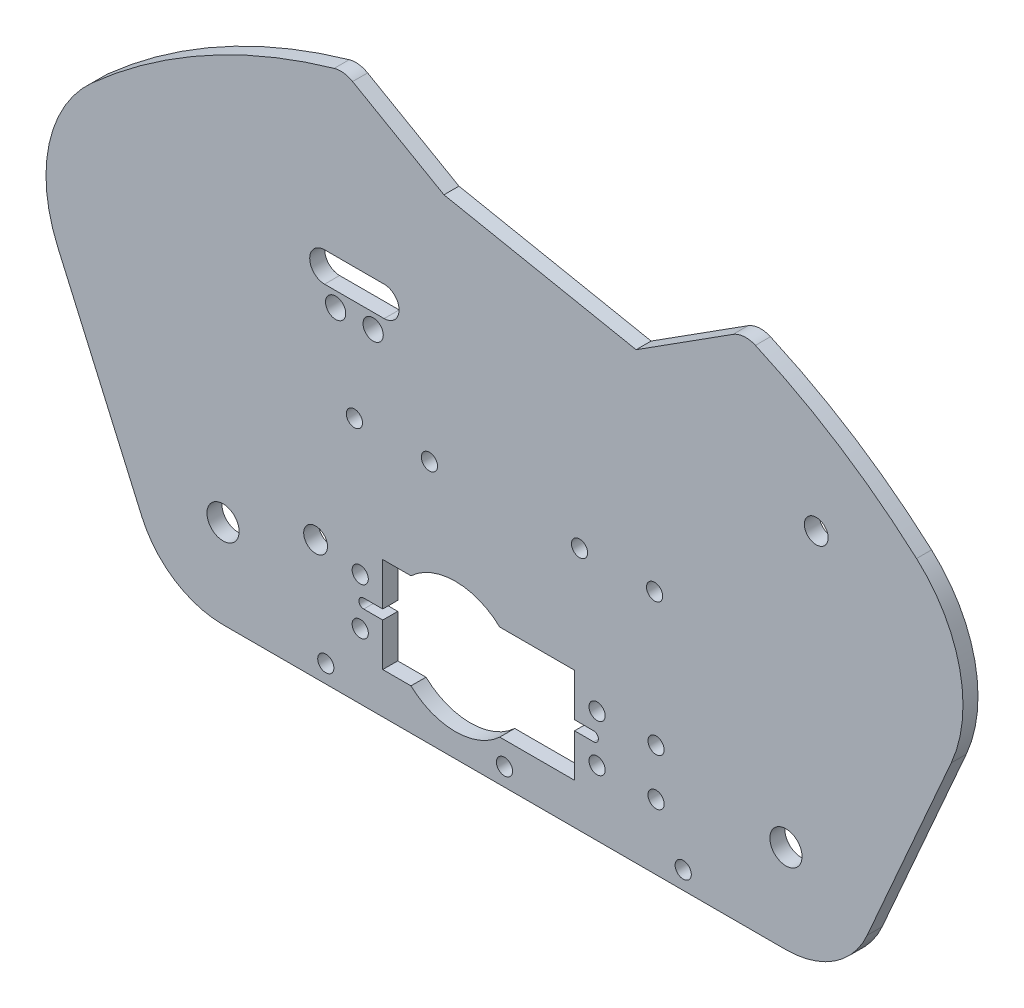
SolidWorks part; units mm, degrees
ref_plane "Front Plane" through (0, 0, 0) normal (0, 0, 1) x (1, 0, 0)
ref_plane "Top Plane" through (0, 0, 0) normal (0, 1, 0) x (1, 0, 0)
ref_plane "Right Plane" through (0, 0, 0) normal (1, 0, 0) x (0, 0, -1)
sketch "Sketch1" plane through (0, 0, 0) normal (0, 0, 1) x (1, 0, 0)
  line L8 (0, 18.9078) -> (120.015, 18.9078) construction
  line L18 (155.2575, 52.1157) -> (-35.2425, 52.1157) construction
  line L37 (0, 0) -> (120.015, 0)
  line L42 (19.7347, 25.5664) -> (0, 18.9078) construction
  line L54 (155.2575, 52.1157) -> (137.3256, 11.3022)
  line L55 (60.0075, 52.1157) -> (60.0075, 18.9078) construction
  line L56 (-35.2425, 52.1157) -> (-17.3106, 11.3022)
  line L58 (147.8628, 86.1549) -> (-27.8478, 86.1549) construction
  circle A21 centre (120.015, 18.9078) radius 3.429
  circle A22 centre (0, 18.9078) radius 3.429
  arc A25 (137.3256, 11.3022) -> (120.015, 0) centre (120.015, 18.9078) cw
  arc A26 (0, 0) -> (-17.3106, 11.3022) centre (0, 18.9078) cw
  circle A27 centre (19.7347, 25.5664) radius 2.54
  arc A28 (147.8628, 86.1549) -> (-27.8478, 86.1549) centre (60.0075, -12.2157) ccw
  arc A29 (147.8628, 86.1549) -> (155.2575, 52.1157) centre (128.1135, 64.0417) cw
  arc A30 (-27.8478, 86.1549) -> (-35.2425, 52.1157) centre (-8.0985, 64.0417) ccw
  dimension "D5" = 18.9078
  dimension "D8" = 29.6484
  dimension "D3" = 52.1157
  dimension "D2" = 6.858
  dimension "D10" = 5.08
  dimension "D1" = 190.5
  dimension "D4" = 20.8278
  dimension "D6" = 18.645
  dimension "D7" = 120.015
  dimension "D9" = 34.0392
extrude "Boss-Extrude1" add sketch "Sketch1" along normal blind 3.2004
sketch "Sketch2" plane through (0, 0, 0) normal (0, 0, -1) x (-1, 0, 0)
  line L1 (-155.2575, 52.1157) -> (35.2425, 52.1157) construction
  line L28 (-92.0115, 52.1157) -> (-76.0095, 52.1157) construction
  line L29 (-76.0095, 52.1157) -> (-44.0055, 52.1157) construction
  line L30 (-44.0055, 52.1157) -> (-28.0035, 52.1157) construction
  circle A0 centre (-92.0115, 52.1157) radius 1.7272
  circle A1 centre (-76.0095, 52.1157) radius 1.7272
  circle A2 centre (-44.0055, 52.1157) radius 1.7272
  circle A3 centre (-28.0035, 52.1157) radius 1.7272
  point P11 (-36.0045, 52.1157)
  point P16 (-84.0105, 52.1157)
  dimension "D3" = 3.4544
  dimension "D2" = 16.002
  dimension "D4" = 48.006
extrude "Cut-Extrude1" cut sketch "Sketch2" against normal blind 3.2004
sketch "Sketch5" plane through (0, 0, 0) normal (0, 0, -1) x (-1, 0, 0)
  line L0 (0, 18.9078) -> (-120.015, 18.9078) construction
  line L5 (-92.3222, 13.9078) -> (-92.3222, 23.9078) construction
  line L6 (-74.944, 29.0678) -> (-74.944, 8.7478)
  line L7 (-34.05, 29.0678) -> (-34.05, 8.7478)
  line L12 (-54.497, 29.0678) -> (-54.497, 8.7478) construction
  line L13 (-79.747, 13.9078) -> (-79.747, 23.9078) construction
  line L14 (-29.247, 13.9078) -> (-29.247, 23.9078) construction
  line L15 (-79.747, 18.9078) -> (-29.247, 18.9078) construction
  line L19 (-92.3222, 18.9078) -> (-79.747, 18.9078) construction
  line L21 (-74.944, 8.7478) -> (-34.05, 8.7478)
  line L25 (-74.944, 29.0678) -> (-34.05, 29.0678)
  circle A0 centre (-79.747, 23.9078) radius 1.7272
  circle A1 centre (-29.247, 13.9078) radius 1.7272
  circle A2 centre (-29.247, 23.9078) radius 1.7272
  circle A3 centre (-79.747, 13.9078) radius 1.7272
  circle A6 centre (0, 18.9078) radius 3.429 construction
  circle A9 centre (-92.3222, 23.9078) radius 1.7272
  circle A10 centre (-92.3222, 13.9078) radius 1.7272
  point P8 (-44.45, 18.9078)
  point P9 (-54.497, 18.9078)
  dimension "D2" = 3.4544
  dimension "D3" = 40.894
  dimension "D5" = 10.4
  dimension "D1" = 50.5
  dimension "D4" = 20.32
  dimension "D6" = 44.45
  dimension "D7" = 10
  dimension "D8" = 12.5752
extrude "Cut-Extrude3" cut sketch "Sketch5" against normal through all
sketch "Sketch6" plane through (0, 0, 3.2004) normal (0, 0, 1) x (1, 0, 0)
  line L3 (79.747, 18.9078) -> (29.247, 18.9078) construction
  line L4 (29.986, 19.9238) -> (34.05, 19.9238)
  line L5 (29.986, 19.9238) -> (29.986, 17.8918) construction
  line L7 (29.986, 17.8918) -> (34.05, 17.8918)
  line L8 (34.05, 19.9238) -> (34.05, 17.8918)
  line L9 (74.944, 19.9238) -> (79.008, 19.9238)
  line L10 (74.944, 19.9238) -> (74.944, 17.8918)
  line L11 (74.944, 17.8918) -> (79.008, 17.8918)
  line L12 (79.008, 19.9238) -> (79.008, 17.8918) construction
  line L13 (34.05, 8.7478) -> (34.05, 29.0678) construction
  line L14 (74.944, 29.0678) -> (74.944, 8.7478) construction
  arc A6 (79.008, 19.9238) -> (79.008, 17.8918) centre (79.008, 18.9078) cw
  arc A7 (29.986, 19.9238) -> (29.986, 17.8918) centre (29.986, 18.9078) ccw
  point P22 (34.05, 18.9078)
  point P23 (74.944, 18.9078)
  dimension "D4" = 4.064
  dimension "D5" = 2.032
extrude "Cut-Extrude4" cut sketch "Sketch6" against normal up to surface (3.2004 mm away) up to face at (90.595, 23.9078, 0)
sketch "Sketch8" plane through (0, 0, 3.2004) normal (0, 0, 1) x (1, 0, 0)
  line L0 (21.9075, 3.81) -> (98.1075, 3.81) construction
  line L1 (60.0075, 7.62) -> (60.0075, 0) construction
  line L2 (0, 0) -> (120.015, 0) construction
  circle A0 centre (21.9075, 3.81) radius 1.7272
  circle A1 centre (60.0075, 3.81) radius 1.7272
  circle A2 centre (98.1075, 3.81) radius 1.7272
  point P6 (60.0075, 3.81)
  dimension "D3" = 3.4544
  dimension "D1" = 76.2
  dimension "D2" = 7.62
extrude "Cut-Extrude6" cut sketch "Sketch8" against normal up to surface (3.2004 mm away) up to face at (54.497, 18.9078, 0)
sketch "Sketch9" plane through (0, 0, 3.2004) normal (0, 0, 1) x (1, 0, 0)
  line L0 (146.2916, 31.7089) -> (111.6995, 46.9073) construction
  line L1 (111.6995, 46.9073) -> (126.4745, 80.5358) construction
  line L3 (137.3256, 11.3022) -> (155.2575, 52.1157) construction
  circle A0 centre (126.4745, 80.5358) radius 2.54
  circle A2 centre (19.7347, 25.5664) radius 2.54 construction
  dimension "D1" = 37.7837
  dimension "D2" = 36.7311
extrude "Cut-Extrude7" cut sketch "Sketch9" against normal up to surface (3.2004 mm away) up to face at (20.1803, 3.81, 0)
sketch "Sketch10" plane through (0, 0, 3.2004) normal (0, 0, 1) x (1, 0, 0)
  line L0 (25.7818, 115.1575) -> (47.0979, 102.9327)
  line L1 (47.0979, 102.9327) -> (88.0719, 94.8169)
  line L2 (88.0719, 94.8169) -> (110.9924, 109.4226)
  arc A1 (147.8628, 86.1549) -> (-27.8478, 86.1549) centre (60.0075, -12.2157) ccw construction
  arc A2 (110.9924, 109.4226) -> (25.7818, 115.1575) centre (60.0075, -12.2157) ccw
  point P0 (43.3022, 118.6134)
  dimension "D1" = 41.77
  dimension "D2" = 27.1786
  dimension "D3" = 17.858
  dimension "D4" = 24.5728
  dimension "D5" = 161.37
  dimension "D6" = 136.29
extrude "Cut-Extrude8" cut sketch "Sketch10" against normal up to surface (3.2004 mm away) up to face at (123.9345, 80.5358, 0)
fillet "Fillet1" radius 5.08 2 edges at (25.7818, 115.1575, 1.6002) (110.9924, 109.4226, 1.6002)
sketch "Sketch12" plane through (0, 0, 3.2004) normal (0, 0, 1) x (1, 0, 0)
  line L1 (21.6535, 80.0557) -> (34.3535, 80.0557)
  line L2 (21.6535, 80.0557) -> (21.6535, 73.7057) construction
  line L3 (21.6535, 73.7057) -> (34.3535, 73.7057)
  line L4 (34.3535, 80.0557) -> (34.3535, 73.7057) construction
  line L7 (0, 0) -> (120.015, 0) construction
  line L9 (28.0035, 73.7057) -> (28.0035, 70.5307) construction
  line L11 (24.003, 70.5307) -> (32.004, 70.5307) construction
  arc A0 (34.3535, 80.0557) -> (34.3535, 73.7057) centre (34.3535, 76.8807) cw
  arc A1 (21.6535, 80.0557) -> (21.6535, 73.7057) centre (21.6535, 76.8807) ccw
  circle A6 centre (28.0035, 52.1157) radius 1.7272 construction
  circle A7 centre (24.003, 70.5307) radius 2.159
  circle A8 centre (32.004, 70.5307) radius 2.159
  dimension "D3" = 6.35
  dimension "D4" = 21.59
  dimension "D5" = 4.318
  dimension "D1" = 12.7
  dimension "D2" = 6.35
  dimension "D6" = 3.175
  dimension "D7" = 8.001
extrude "Cut-Extrude10" cut sketch "Sketch12" against normal up to surface (3.2004 mm away) up to face at (63.4319, 67.4563, 0)
sketch "Sketch13" plane through (0, 0, 3.2004) normal (0, 0, 1) x (1, 0, 0)
  line L0 (79.747, 18.9078) -> (29.247, 18.9078) construction
  circle A0 centre (49.53, 18.9078) radius 13.8852
  dimension "D1" = 27.7704
  dimension "D2" = 5.08
extrude "Cut-Extrude11" cut sketch "Sketch13" against normal up to surface (3.2004 mm away) up to face at (28.0035, 76.8807, 0)
